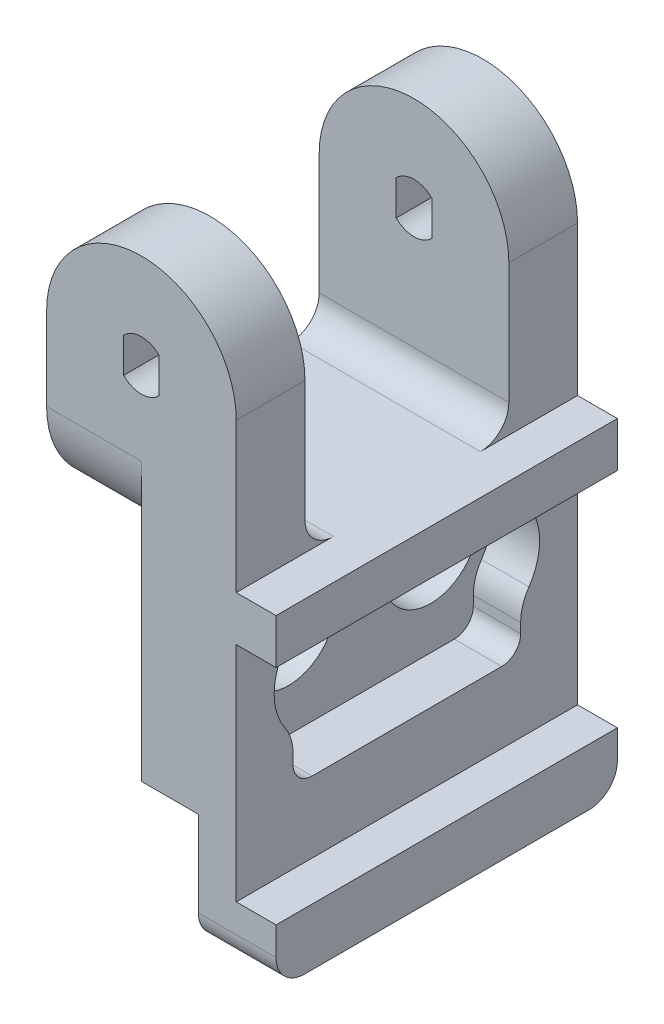
SolidWorks part; units mm, degrees
ref_plane "Front Plane" through (0, 0, 0) normal (0, 0, 1) x (1, 0, 0)
ref_plane "Top Plane" through (0, 0, 0) normal (0, 1, 0) x (1, 0, 0)
ref_plane "Right Plane" through (0, 0, 0) normal (1, 0, 0) x (0, 0, -1)
sketch "Sketch1" plane through (0, 0, 0) normal (0, 0, 1) x (1, 0, 0)
  line L2 (44.2641, -14) -> (44.2641, -59)
  line L3 (44.2641, -59) -> (64.2641, -59)
  line L4 (64.2641, -14) -> (64.2641, -59)
  arc A0 (64.2641, -14) -> (44.2641, -14) centre (54.2641, -14) ccw
  dimension "D1" = 45
extrude "Boss-Extrude1" add sketch "Sketch1" along normal blind 8 contours L2 L3 L4 A0
sketch "Sketch2" plane through (0, 0, -20) normal (0, 0, -1) x (-1, 0, 0)
  line L3 (-64.2641, -14) -> (-64.2641, -59)
  line L4 (-64.2641, -59) -> (-44.2641, -59)
  line L5 (-44.2641, -59) -> (-44.2641, -14)
  line L6 (-64.2641, -14) -> (-64.2641, -59)
  line L7 (-64.2641, -59) -> (-44.2641, -59)
  line L8 (-44.2641, -59) -> (-44.2641, -14)
  arc A1 (-44.2641, -14) -> (-64.2641, -14) centre (-54.2641, -14) ccw
  arc A2 (-44.2641, -14) -> (-64.2641, -14) centre (-54.2641, -14) ccw
  dimension "D1" = 0
extrude "Boss-Extrude2" add sketch "Sketch2" along normal blind 8 separate body
sketch "Sketch3" plane through (0, 0, 0) normal (0, 0, -1) x (-1, 0, 0)
  line L0 (-44.2641, -59) -> (-44.2641, -14) construction
  line L1 (-64.2641, -59) -> (-44.2641, -59)
  line L2 (-64.2641, -59) -> (-64.2641, -29.75)
  line L3 (-64.2641, -29.75) -> (-44.2641, -29.75)
  line L4 (-44.2641, -59) -> (-44.2641, -29.75)
extrude "Boss-Extrude3" add sketch "Sketch3" along normal up to surface (20 mm away) up to face at (54.2641, -34, -20)
sketch "Sketch4" plane through (0, 0, 8) normal (0, 0, 1) x (1, 0, 0)
  line L0 (52.3891, -12.1629) -> (52.3891, -15.8371)
  line L1 (56.1391, -12.1629) -> (56.1391, -15.8371)
  arc A0 (56.1391, -12.1629) -> (52.3891, -12.1629) centre (54.2641, -14) ccw
  arc A1 (52.3891, -15.8371) -> (56.1391, -15.8371) centre (54.2641, -14) ccw
  dimension "D1" = 3.75
  dimension "D2" = 1.875
extrude "Cut-Extrude1" cut sketch "Sketch4" against normal up to surface (36 mm away) up to face at (54.2641, -34, -28)
sketch "Sketch5" plane through (0, 0, -20) normal (0, 0, 1) x (1, 0, 0)
  line L3 (44.2641, -14) -> (44.2641, -29.75)
  line L4 (44.2641, -29.75) -> (64.2641, -29.75)
  line L5 (64.2641, -29.75) -> (64.2641, -14)
  line L6 (44.2641, -14) -> (44.2641, -29.75)
  line L7 (44.2641, -29.75) -> (64.2641, -29.75)
  line L8 (64.2641, -29.75) -> (64.2641, -14)
  arc A1 (64.2641, -14) -> (44.2641, -14) centre (54.2641, -14) ccw
  arc A2 (64.2641, -14) -> (44.2641, -14) centre (54.2641, -14) ccw
  dimension "D1" = 0
extrude "Cut-Extrude2" cut sketch "Sketch5" against normal blind 0.75
sketch "Sketch6" plane through (0, 0, 0) normal (0, 0, -1) x (-1, 0, 0)
  line L3 (-64.2641, -29.75) -> (-44.2641, -29.75)
  line L4 (-44.2641, -29.75) -> (-44.2641, -14)
  line L5 (-64.2641, -14) -> (-64.2641, -29.75)
  line L6 (-64.2641, -29.75) -> (-44.2641, -29.75)
  line L7 (-44.2641, -29.75) -> (-44.2641, -14)
  line L8 (-64.2641, -14) -> (-64.2641, -29.75)
  arc A1 (-44.2641, -14) -> (-64.2641, -14) centre (-54.2641, -14) ccw
  arc A2 (-44.2641, -14) -> (-64.2641, -14) centre (-54.2641, -14) ccw
  dimension "D1" = 0
extrude "Cut-Extrude3" cut sketch "Sketch6" against normal blind 0.75
sketch "Sketch7" plane through (0, -59, 0) normal (0, -1, 0) x (1, 0, 0)
  line L4 (44.2641, 8) -> (44.2641, -28)
  line L5 (44.2641, -28) -> (64.2641, -28)
  line L6 (64.2641, -28) -> (64.2641, 8)
  line L7 (64.2641, 8) -> (44.2641, 8)
  line L8 (44.2641, 8) -> (44.2641, -28)
  line L9 (44.2641, -28) -> (64.2641, -28)
  line L10 (64.2641, -28) -> (64.2641, 8)
  line L11 (64.2641, 8) -> (44.2641, 8)
  dimension "D1" = 0
extrude "Boss-Extrude4" add sketch "Sketch7" along normal blind 5
fillet "Fillet1" radius 3 2 edges at (54.2641, -64, 8) (54.2641, -64, -28)
sketch "Sketch9" plane through (44.2641, 0, 0) normal (-1, 0, 0) x (0, 0, 1)
  line L0 (-20.75, -29.75) -> (0.75, -29.75) construction
  line L1 (-31.0505, -68.0926) -> (10.4848, -68.0926)
  line L2 (-31.0505, -68.0926) -> (-31.0505, -32.75)
  line L3 (-31.0505, -32.75) -> (10.4848, -32.75)
  line L4 (10.4848, -68.0926) -> (10.4848, -32.75)
  circle A0 centre (69.629, -68.0926) radius 10 construction
  dimension "D1" = 3
extrude "Cut-Extrude4" cut sketch "Sketch9" against normal blind 10
sketch "Sketch10" plane through (54.2641, 0, 0) normal (-1, 0, 0) x (0, 0, 1)
  line L0 (-17.5, -41) -> (-2.5, -41) construction
  line L1 (-10, -26.75) -> (-10, -41) construction
  line L3 (-10, -41) -> (-10, -61) construction
  circle A0 centre (-2.5, -41) radius 5
  circle A1 centre (-17.5, -41) radius 5
extrude "Cut-Extrude5" cut sketch "Sketch10" against normal blind 10
sketch "Sketch12" plane through (64.2641, 0, 0) normal (1, 0, 0) x (0, 0, -1)
  line L0 (22, -47.4807) -> (22, -48.5)
  line L1 (20, -50.5) -> (0, -50.5)
  line L2 (-2, -48.5) -> (-2, -47.4807)
  line L3 (17.5, -34.5) -> (2.5, -34.5)
  line L4 (10, -50.5) -> (10, -47.4807) construction
  line L5 (10, -29.75) -> (10, -34.5) construction
  line L8 (20.75, -29.75) -> (-0.75, -29.75) construction
  line L9 (10, -34.5) -> (10, -37.5521) construction
  arc A0 (2.5, -34.5) -> (-2.8696, -44.663) centre (2.5, -41) ccw
  arc A1 (22.8696, -44.663) -> (17.5, -34.5) centre (17.5, -41) ccw
  arc A2 (0, -50.5) -> (-2, -48.5) centre (0, -48.5) cw
  arc A3 (22, -48.5) -> (20, -50.5) centre (20, -48.5) cw
  arc A4 (-2.8696, -44.663) -> (-2, -47.4807) centre (-7, -47.4807) cw
  arc A5 (22.8696, -44.663) -> (22, -47.4807) centre (27, -47.4807) ccw
extrude "Cut-Extrude6" cut sketch "Sketch12" against normal blind 5
fillet "Fillet4" radius 3 2 edges at (54.2641, -29.75, 0.75) (54.2641, -29.75, -20.75)
sketch "Sketch13" plane through (64.2641, 0, 0) normal (1, 0, 0) x (0, 0, -1)
  line L0 (-8, -14) -> (-8, -61) construction
  line L1 (-8, -29.75) -> (28, -29.75)
  line L2 (-8, -29.75) -> (-8, -34.5)
  line L3 (-8, -34.5) -> (28, -34.5)
  line L4 (28, -29.75) -> (28, -34.5)
  line L5 (28, -14) -> (28, -61) construction
  line L8 (-8, -58) -> (28, -58)
  line L10 (25, -64) -> (-5, -64) construction
  line L11 (25, -64) -> (-5, -64)
  line L12 (-8, -58) -> (-8, -61)
  line L13 (28, -58) -> (28, -61)
  arc A0 (-8, -61) -> (-5, -64) centre (-5, -61) ccw construction
  arc A1 (25, -64) -> (28, -61) centre (25, -61) ccw construction
  arc A2 (-8, -61) -> (-5, -64) centre (-5, -61) ccw
  arc A3 (25, -64) -> (28, -61) centre (25, -61) ccw
  point P12 (28, 59.0111)
  point P13 (28, -16.3401)
  point P18 (28, -33.6799)
extrude "Boss-Extrude5" add sketch "Sketch13" along normal up to surface (4.2 mm away)
sketch "Sketch14" plane through (0, 0, 8) normal (0, 0, 1) x (1, 0, 0)
  line L1 (54.2641, -64) -> (60.2641, -64)
  line L2 (54.2641, -64) -> (54.2641, -52)
  line L3 (54.2641, -52) -> (60.2641, -52)
  line L4 (60.2641, -64) -> (60.2641, -52)
extrude "Cut-Extrude7" cut sketch "Sketch14" against normal up to surface (36 mm away) up to face at (60.6641, -37.5, -28)
fillet "Fillet5" radius 10 2 edges at (49.2641, -32.75, -28) (49.2641, -32.75, 8)
